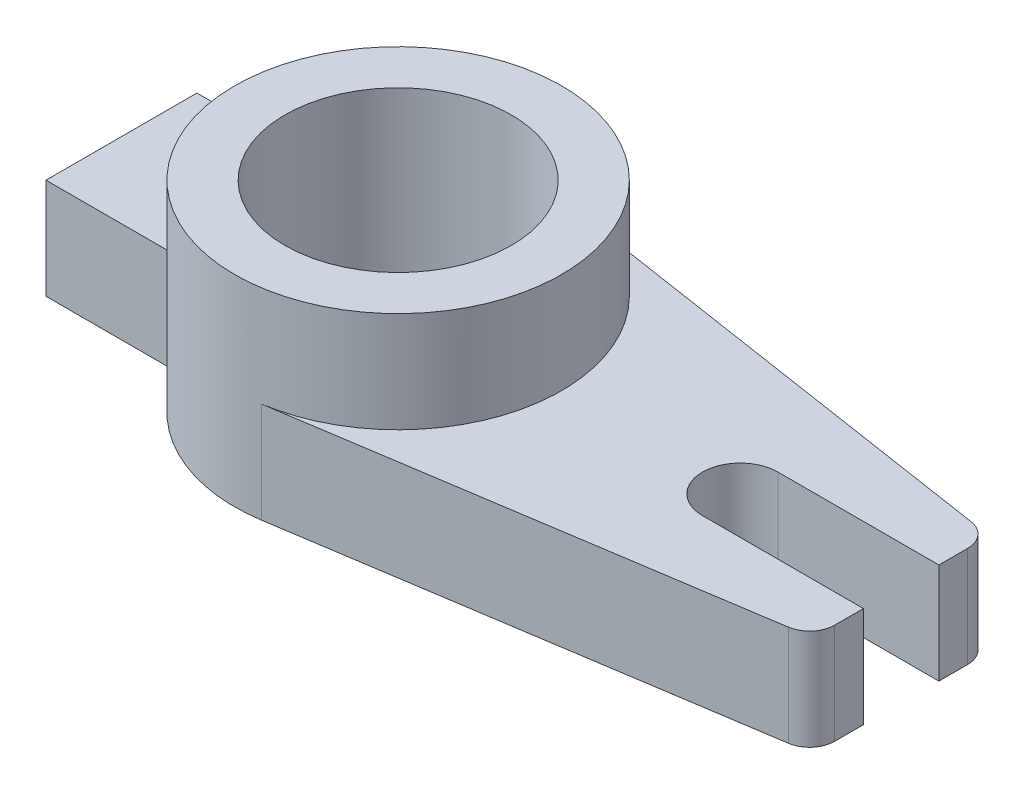
SolidWorks part; units mm, degrees
ref_plane "Front Plane" through (0, 0, 0) normal (0, 0, 1) x (1, 0, 0)
ref_plane "Top Plane" through (0, 0, 0) normal (0, 1, 0) x (1, 0, 0)
ref_plane "Right Plane" through (0, 0, 0) normal (1, 0, 0) x (0, 0, -1)
sketch "Sketch1" plane through (0, 0, 0) normal (0, 1, 0) x (1, 0, 0)
  line L0 (68, 7.5) -> (100, 7.5)
  line L1 (100, 7.5) -> (100, 13.2103)
  line L2 (95.7602, 18.1522) -> (4.9411, 32.1222)
  line L3 (0, 0) -> (95.3149, 0) construction
  line L6 (-55, -15) -> (-55, 15)
  line L7 (-55, 15) -> (-28.8314, 15)
  line L8 (68, -7.5) -> (100, -7.5)
  line L9 (100, -7.5) -> (100, -13.2103)
  line L10 (95.7602, -18.1522) -> (4.9411, -32.1222)
  line L11 (-55, -15) -> (-28.8314, -15)
  circle A0 centre (0, 0) radius 22.5
  circle A1 centre (0, 0) radius 32.5
  arc A2 (68, 7.5) -> (68, -7.5) centre (68, 0) ccw
  arc A3 (100, 13.2103) -> (95.7602, 18.1522) centre (95, 13.2103) ccw
  arc A4 (100, -13.2103) -> (95.7602, -18.1522) centre (95, -13.2103) cw
  point P9 (0, 0)
  point P15 (100, -17.5)
  point P27 (-55, 0)
  point P28 (100, 17.5)
  dimension "D1" = 5
  dimension "D3" = 65
  dimension "D4" = 45
  dimension "D2" = 35
  dimension "D5" = 30
  dimension "D6" = 55
  dimension "D7" = 100
  dimension "D8" = 32
  dimension "D9" = 15
extrude "Boss-Extrude4" add sketch "Sketch1" along normal blind 20 contours L6 L3 A1 L7 | A1 L3 A0 | L3 L6 L11 A1 | L3 A1 A0 | A1 L3 A2 L0 L1 A3 L2 | L3 A1 L10 A4 L9 L8 A2 region at (55.8895, 0, -14.3822) region at (55.8895, 0, 14.3822) region at (23.9685, 0, 20.5635) region at (-43.1283, 0, 0)
extrude "Boss-Extrude5" add sketch "Sketch1<6>" along normal blind 40 contours A1 L3 A0 | L3 A1 A0 region at (23.9685, 0, 20.5635)
sketch "Sketch1<6>" plane through (0, 0, 0) normal (0, 1, 0) x (1, 0, 0) same geometry as "Sketch1"
